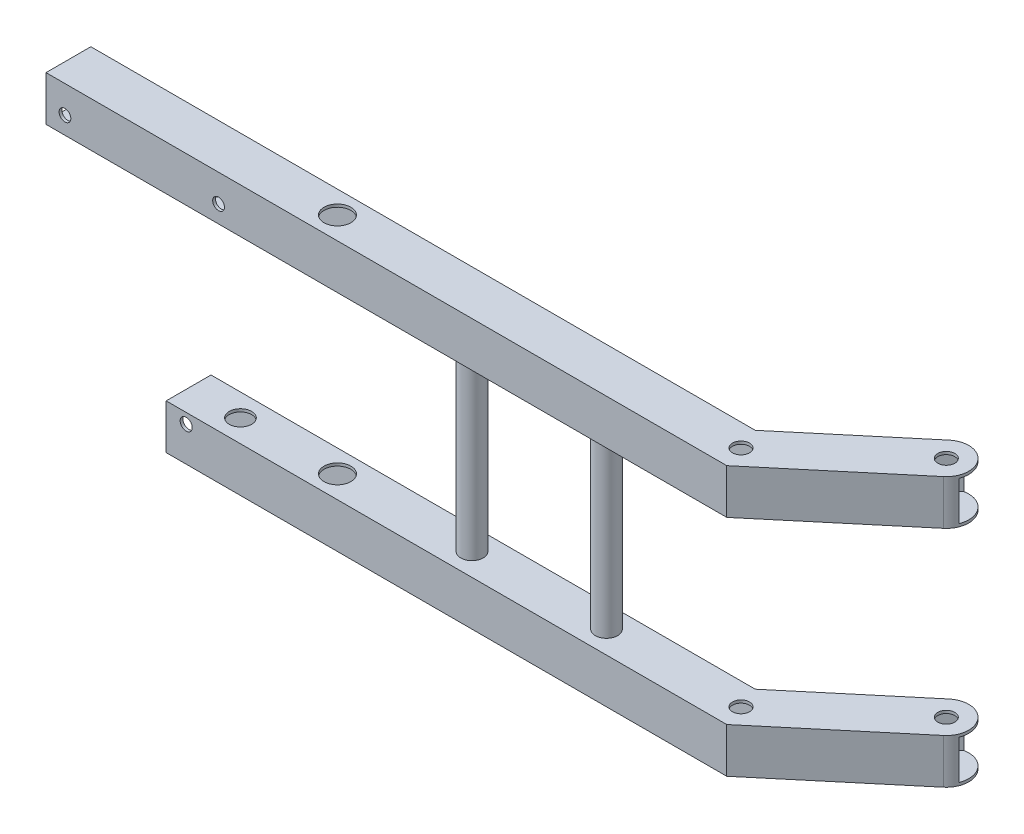
SolidWorks part; units mm, degrees
ref_plane "Front Plane" through (0, 0, 0) normal (0, 0, 1) x (1, 0, 0)
ref_plane "Top Plane" through (0, 0, 0) normal (0, 1, 0) x (1, 0, 0)
ref_plane "Right Plane" through (0, 0, 0) normal (1, 0, 0) x (0, 0, -1)
sketch "Sketch4" plane through (0, 0, 0) normal (0, 1, 0) x (1, 0, 0)
  line L0 (0, 0) -> (-254, 0) construction
  line L1 (0, 0) -> (91.1351, 76.4714) construction
  line L2 (-254, -12.7) -> (-254, 12.7)
  line L3 (4.6224, -12.7) -> (-4.6224, 12.7) construction
  line L4 (-254, 12.7) -> (-4.6224, 12.7)
  line L5 (99.2985, 66.7427) -> (82.9717, 86.2002)
  line L6 (82.9717, 86.2002) -> (-4.6224, 12.7)
  line L7 (-254, -12.7) -> (4.6224, -12.7)
  line L8 (4.6224, -12.7) -> (99.2985, 66.7427)
  circle A0 centre (0, 0) radius 4.826
  circle A1 centre (63.237, 53.0621) radius 4.826
  circle A3 centre (-228.6, 0) radius 7.62
  point P7 (-254, 0)
  point P10 (0, 0)
  point P13 (91.1351, 76.4714)
  dimension "D2" = 9.652
  dimension "D7" = 15.24
  dimension "D1" = 82.55
  dimension "D3" = 25.4
  dimension "D5" = 25.4
  dimension "D6" = 228.6
extrude "Boss-Extrude3" add sketch "Sketch4" along normal blind 152.4
sketch "Sketch5" plane through (-254, 0, 0) normal (-1, 0, 0) x (0, 0, 1)
  line L0 (0, 152.4) -> (0, 0) construction
  line L3 (-12.7, 152.4) -> (12.7, 152.4) construction
  line L6 (-12.7, 0) -> (12.7, 0) construction
  line L7 (11.1125, 128.5875) -> (-11.1125, 128.5875)
  line L8 (11.1125, 128.5875) -> (11.1125, 150.8125)
  line L9 (11.1125, 150.8125) -> (-11.1125, 150.8125)
  line L10 (-11.1125, 128.5875) -> (-11.1125, 150.8125)
  line L11 (11.1125, 128.5875) -> (-11.1125, 150.8125) construction
  line L12 (11.1125, 150.8125) -> (-11.1125, 128.5875) construction
  line L13 (-12.7, 127) -> (12.7, 127)
  line L14 (-12.7, 152.4) -> (-12.7, 0) construction
  line L15 (12.7, 152.4) -> (12.7, 0) construction
  line L16 (11.1125, 1.5875) -> (-11.1125, 1.5875)
  line L17 (11.1125, 1.5875) -> (11.1125, 23.8125)
  line L18 (11.1125, 23.8125) -> (-11.1125, 23.8125)
  line L19 (-11.1125, 1.5875) -> (-11.1125, 23.8125)
  line L20 (11.1125, 1.5875) -> (-11.1125, 23.8125) construction
  line L21 (11.1125, 23.8125) -> (-11.1125, 1.5875) construction
  line L22 (-12.7, 25.4) -> (12.7, 25.4)
  line L23 (-12.7, 25.4) -> (-12.7, 127)
  line L24 (12.7, 127) -> (12.7, 25.4)
  point P12 (0, 139.7)
  point P19 (0, 12.7)
  point P26 (0, 25.4)
  dimension "D1" = 1.5875
  dimension "D2" = 12.7
  dimension "D3" = 12.7
  dimension "D4" = 1.5875
  dimension "D5" = 12.7
  dimension "D6" = 12.7
extrude "Cut-Extrude2" cut sketch "Sketch5" against normal up to vertex (258.6224 mm away) up to point (4.6224, 152.4, 12.7)
sketch "Sketch6" plane through (91.1351, 0, -76.4714) normal (0.766, 0, -0.6428) x (-0.6428, 0, -0.766)
  line L0 (12.7, 127) -> (-12.7, 127)
  line L1 (12.7, 152.4) -> (12.7, 0) construction
  line L3 (0, 0) -> (0, 152.4) construction
  line L4 (-12.7, 0) -> (12.7, 0) construction
  line L5 (-12.7, 152.4) -> (12.7, 152.4) construction
  line L6 (-12.7, 152.4) -> (-12.7, 0) construction
  line L7 (-11.1125, 128.5875) -> (11.1125, 128.5875)
  line L8 (-11.1125, 128.5875) -> (-11.1125, 150.8125)
  line L9 (-11.1125, 150.8125) -> (11.1125, 150.8125)
  line L10 (11.1125, 128.5875) -> (11.1125, 150.8125)
  line L11 (-11.1125, 128.5875) -> (11.1125, 150.8125) construction
  line L12 (-11.1125, 150.8125) -> (11.1125, 128.5875) construction
  line L13 (12.7, 25.4) -> (-12.7, 25.4)
  line L14 (-11.1125, 1.5875) -> (11.1125, 1.5875)
  line L15 (-11.1125, 1.5875) -> (-11.1125, 23.8125)
  line L16 (-11.1125, 23.8125) -> (11.1125, 23.8125)
  line L17 (11.1125, 1.5875) -> (11.1125, 23.8125)
  line L18 (-11.1125, 1.5875) -> (11.1125, 23.8125) construction
  line L19 (-11.1125, 23.8125) -> (11.1125, 1.5875) construction
  line L20 (-12.7, 25.4) -> (-12.7, 127)
  line L21 (12.7, 127) -> (12.7, 25.4)
  point P5 (0, 127)
  point P12 (0, 139.7)
  point P18 (0, 25.4)
  point P19 (0, 12.7)
  dimension "D1" = 1.5875
  dimension "D2" = 12.7
  dimension "D3" = 12.7
  dimension "D4" = 1.5875
  dimension "D5" = 25.4
  dimension "D6" = 12.7
extrude "Cut-Extrude3" cut sketch "Sketch6" against normal up to vertex (123.5909 mm away) up to point (4.6224, 152.4, 12.7)
sketch "Sketch7" plane through (0, 152.4, 0) normal (0, 1, 0) x (1, 0, 0)
  line L0 (71.4004, 43.3334) -> (55.0736, 62.7909) construction
  line L1 (82.9717, 86.2002) -> (-4.6224, 12.7) construction
  line L2 (4.6224, -12.7) -> (99.2985, 66.7427) construction
  line L3 (55.0736, 62.7909) -> (14.2925, 190.3795)
  line L4 (14.2925, 190.3795) -> (153.8443, 116.5917)
  line L5 (153.8443, 116.5917) -> (141.5355, -3.4731)
  line L6 (141.5355, -3.4731) -> (71.4004, 43.3334)
  arc A0 (55.0736, 62.7909) -> (71.4004, 43.3334) centre (63.237, 53.0621) cw
  point P6 (63.237, 53.0621)
  point P7 (63.237, 53.0621)
extrude "Cut-Extrude4" cut sketch "Sketch7" against normal up to surface (152.4 mm away) up to face at (-54.2883, 0, -25.4905)
sketch "Sketch8" plane through (0, 127, 0) normal (0, -1, 0) x (1, 0, 0)
  line L0 (0, 0) -> (-228.6, 0) construction
  circle A0 centre (-76.2, 0) radius 6.35
  circle A1 centre (-152.4, 0) radius 6.35
  dimension "D3" = 12.7
  dimension "D1" = 76.2
  dimension "D2" = 76.2
extrude "Boss-Extrude4" add sketch "Sketch8" along normal up to surface (101.6 mm away) up to face at (-61.9662, 25.4, -19.0479)
sketch "Sketch9" plane through (-254, 0, 0) normal (-1, 0, 0) x (0, 0, 1)
  line L0 (-12.7, 152.4) -> (12.7, 152.4)
  line L1 (12.7, 152.4) -> (12.7, 127)
  line L2 (12.7, 127) -> (-12.7, 127)
  line L3 (-12.7, 152.4) -> (-12.7, 127) construction
  line L4 (12.7, 127) -> (-12.7, 127) construction
  line L5 (-12.7, 127) -> (-12.7, 152.4)
  line L6 (-11.1125, 150.8125) -> (11.1125, 150.8125)
  line L7 (11.1125, 150.8125) -> (11.1125, 128.5875)
  line L8 (11.1125, 128.5875) -> (-11.1125, 128.5875)
  line L9 (-11.1125, 128.5875) -> (-11.1125, 150.8125)
  line L10 (-12.7, 25.4) -> (12.7, 25.4)
  line L11 (12.7, 25.4) -> (12.7, 0)
  line L12 (12.7, 0) -> (-12.7, 0)
  line L13 (-12.7, 0) -> (-12.7, 25.4)
  line L14 (-11.1125, 23.8125) -> (11.1125, 23.8125)
  line L15 (11.1125, 23.8125) -> (11.1125, 1.5875)
  line L16 (11.1125, 1.5875) -> (-11.1125, 1.5875)
  line L17 (-11.1125, 1.5875) -> (-11.1125, 23.8125)
extrude "Boss-Extrude5" add sketch "Sketch9" along normal blind 58.928
sketch "Sketch11" plane through (0, 127, 0) normal (0, -1, 0) x (1, 0, 0)
  line L0 (-312.928, 0) -> (-228.6, 0) construction
  line L1 (-312.928, -12.7) -> (-312.928, 12.7) construction
  circle A0 centre (-271.0548, 0) radius 1.65
  circle A1 centre (-296.0548, 0) radius 1.65
  dimension "D2" = 3.3
  dimension "D1" = 25
extrude "Cut-Extrude6" cut sketch "Sketch11" against normal up to surface (1.5875 mm away) up to face at (0, 128.5875, -4.826)
sketch "Sketch12" plane through (0, 127, 0) normal (0, -1, 0) x (1, 0, 0)
  line L0 (-271.0548, 0) -> (-296.0548, 0) construction
  circle A0 centre (-283.5548, 0) radius 6.35
extrude "Cut-Extrude7" cut sketch "Sketch12" along normal up to surface (103.1875 mm away) up to face at (-228.6, 23.8125, 7.62)
sketch "Sketch13" plane through (-312.928, 0, 0) normal (-1, 0, 0) x (0, 0, 1)
  line L1 (12.7, 152.4) -> (-12.7, 152.4)
  line L2 (12.7, 152.4) -> (12.7, 127)
  line L3 (12.7, 127) -> (-12.7, 127)
  line L4 (-12.7, 152.4) -> (-12.7, 127)
  line L5 (-11.1125, 128.5875) -> (11.1125, 128.5875)
  line L6 (-11.1125, 128.5875) -> (-11.1125, 150.8125)
  line L7 (-11.1125, 150.8125) -> (11.1125, 150.8125)
  line L8 (11.1125, 128.5875) -> (11.1125, 150.8125)
extrude "Boss-Extrude6" add sketch "Sketch13" along normal blind 68.072
sketch "Sketch14" plane through (0, 0, 12.7) normal (0, 0, 1) x (1, 0, 0)
  line L0 (-381, 136.87) -> (-288.5629, 136.87) construction
  line L1 (-381, 127) -> (-381, 152.4) construction
  line L2 (4.6224, 127) -> (-381, 127) construction
  line L3 (-312.928, 0) -> (-312.928, 25.4) construction
  line L4 (4.6224, 25.4) -> (-312.928, 25.4) construction
  circle A0 centre (-370.26, 136.87) radius 3.33
  circle A1 centre (-283.26, 136.87) radius 3.33
  circle A2 centre (-301.58, 19.63) radius 3.42
  point P8 (-283.26, 133.54)
  dimension "D2" = 6.66
  dimension "D6" = 6.84
  dimension "D1" = 6.54
  dimension "D3" = 87
  dimension "D4" = 10.74
  dimension "D5" = 11.348
  dimension "D7" = 5.77
extrude "Cut-Extrude8" cut sketch "Sketch14" against normal up to surface (1.5875 mm away) up to face at (-188.8548, 139.7, 11.1125)
